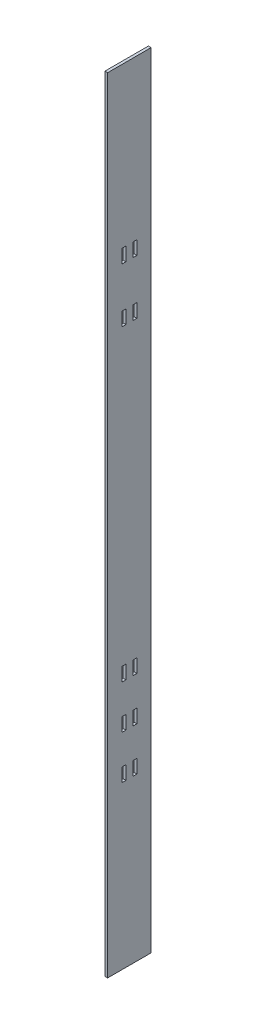
SolidWorks part; units mm, degrees
ref_plane "Front Plane" through (0, 0, 0) normal (0, 0, 1) x (1, 0, 0)
ref_plane "Top Plane" through (0, 0, 0) normal (0, 1, 0) x (1, 0, 0)
ref_plane "Right Plane" through (0, 0, 0) normal (1, 0, 0) x (0, 0, -1)
sketch "Sketch1" plane through (0, 0, 0) normal (1, 0, 0) x (0, 0, -1)
  line L1 (-25.4, 457.2) -> (25.4, 457.2)
  line L2 (-25.4, 457.2) -> (-25.4, -457.2)
  line L3 (-25.4, -457.2) -> (25.4, -457.2)
  line L4 (25.4, 457.2) -> (25.4, -457.2)
  line L5 (-25.4, 457.2) -> (25.4, -457.2) construction
  line L6 (-25.4, -457.2) -> (25.4, 457.2) construction
  point P0 (0, 0)
  dimension "D1" = 914.4
  dimension "D2" = 50.8
extrude "Boss-Extrude1" add sketch "Sketch1" along normal blind 3.175
sketch "Sketch2" plane through (3.175, 0, 0) normal (1, 0, 0) x (0, 0, -1)
  line L0 (-25.4, -457.2) -> (25.4, -457.2) construction
  line L1 (4, -201.6125) -> (8.7625, -201.6125)
  line L2 (4, -201.6125) -> (4, -217.4875)
  line L3 (4, -217.4875) -> (8.7625, -217.4875)
  line L4 (8.7625, -201.6125) -> (8.7625, -217.4875)
  line L5 (4, -201.6125) -> (8.7625, -217.4875) construction
  line L6 (4, -217.4875) -> (8.7625, -201.6125) construction
  point P0 (6.3813, -209.55)
  dimension "D1" = 4.7625
  dimension "D2" = 15.875
  dimension "D3" = 239.7125
  dimension "D4" = 4
extrude "Cut-Extrude1" cut sketch "Sketch2" against normal through all
mirror "Mirror1" about plane through (0, 0, 0) normal (0, 0, 1) of "Cut-Extrude1"
pattern_linear "LPattern1" count 2 spacing 50.8 along (0, 1, 0) count 2 spacing 50.8 along (0, -1, 0) of "Mirror1"
sketch "Sketch3" plane through (3.175, 0, 0) normal (1, 0, 0) x (0, 0, -1)
  line L0 (8.7625, -150.8125) -> (4, -150.8125) construction
  line L1 (4, 207.9625) -> (8.7625, 207.9625)
  line L2 (4, 207.9625) -> (4, 192.0875)
  line L3 (4, 192.0875) -> (8.7625, 192.0875)
  line L4 (8.7625, 207.9625) -> (8.7625, 192.0875)
  line L5 (4, 207.9625) -> (8.7625, 192.0875) construction
  line L6 (4, 192.0875) -> (8.7625, 207.9625) construction
  line L7 (8.7625, -166.6875) -> (8.7625, -150.8125) construction
  line L8 (4, -150.8125) -> (4, -166.6875) construction
  line L9 (0, 0) -> (0, 53.0447) construction
  line L10 (-4, 192.0875) -> (-8.7625, 207.9625) construction
  line L11 (-4, 207.9625) -> (-8.7625, 192.0875) construction
  line L12 (-8.7625, 207.9625) -> (-8.7625, 192.0875)
  line L13 (-4, 192.0875) -> (-8.7625, 192.0875)
  line L14 (-4, 207.9625) -> (-4, 192.0875)
  line L15 (-4, 207.9625) -> (-8.7625, 207.9625)
  point P0 (6.3812, 200.025)
  point P12 (6.3812, 192.0875)
  point P19 (-6.3812, 200.025)
  dimension "D1" = 342.9
extrude "Cut-Extrude2" cut sketch "Sketch3" against normal through all
pattern_linear "LPattern2" count 2 spacing 63.5 along (0, 1, 0) of "Cut-Extrude2"
